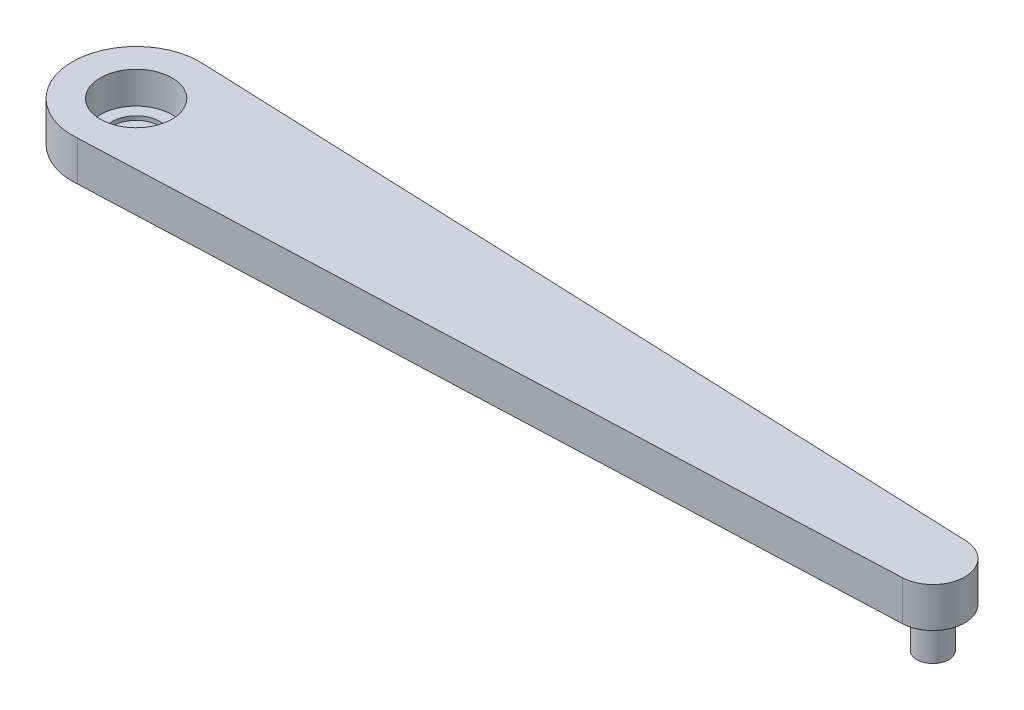
SolidWorks part; units mm, degrees
ref_plane "Piano frontale" through (0, 0, 0) normal (0, 0, 1) x (1, 0, 0)
ref_plane "Piano superiore" through (0, 0, 0) normal (0, 1, 0) x (1, 0, 0)
ref_plane "Piano destro" through (0, 0, 0) normal (1, 0, 0) x (0, 0, -1)
sketch "Sketch1" plane through (0, 0, 0) normal (0, 0, 1) x (1, 0, 0)
  line L2 (0, 0) -> (100, 0)
  line L3 (0.6382, 7.9745) -> (100.1597, 3.9985)
  line L4 (0.6382, -7.9745) -> (100.1597, -3.9985)
  arc A4 (0.6382, 7.9745) -> (0.6382, -7.9745) centre (0, 0) ccw
  arc A5 (100.1597, -3.9985) -> (100.1597, 3.9985) centre (100, 0) ccw
extrude "Boss-Extrude1" add sketch "Sketch1" along normal blind 5 contours A5 L3 A4 L4
sketch "Sketch2" plane through (0, 0, 0) normal (0, 0, -1) x (-1, 0, 0)
  circle A0 centre (0, 0) radius 4.5
extrude "Cut-Extrude1" cut sketch "Sketch2" against normal blind 4
sketch "Sketch7" plane through (0, 0, 4) normal (0, 0, -1) x (-1, 0, 0)
  circle A1 centre (0, 0) radius 3
extrude "Cut-Extrude3" cut sketch "Sketch7" against normal blind 0.5
move or copy body "Body-Move/Copy1" bodies to move or copy 110 copy no rotation origin (0, 0, 11) rotation axis (-1, 0, 0) rotation angle 90
move or copy body "Body-Move/Copy2" bodies to move or copy 111 copy no rotation origin (0, -8, 11) rotation axis (1, 0, 0) rotation angle 180
sketch "Sketch8" plane through (0, -10, 0) normal (0, -1, 0) x (1, 0, 0)
  circle A0 centre (100, 11) radius 2.5
extrude "Boss-Extrude2" add sketch "Sketch8" along normal blind 5
sketch "Sketch9" plane through (0, -15, 0) normal (0, -1, 0) x (1, 0, 0)
  circle A0 centre (100, 11) radius 2.5
  circle A1 centre (100, 11) radius 2
extrude "Cut-Extrude4" cut sketch "Sketch9" against normal blind 4
